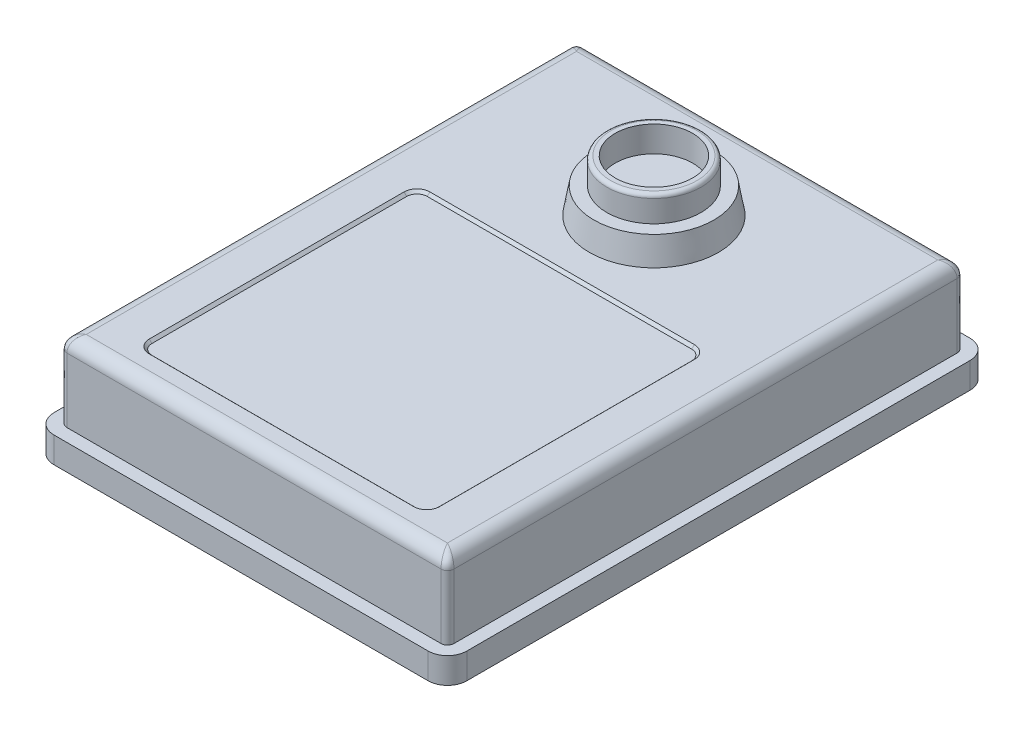
SolidWorks part; units mm, degrees
ref_plane "Front Plane" through (0, 0, 0) normal (0, 0, 1) x (1, 0, 0)
ref_plane "Top Plane" through (0, 0, 0) normal (0, 1, 0) x (1, 0, 0)
ref_plane "Right Plane" through (0, 0, 0) normal (1, 0, 0) x (0, 0, -1)
sketch "Sketch1" plane through (0, 0, 0) normal (0, 1, 0) x (1, 0, 0)
  line L1 (150, 200) -> (-150, 200)
  line L2 (150, 200) -> (150, -200)
  line L3 (150, -200) -> (-150, -200)
  line L4 (-150, 200) -> (-150, -200)
  line L5 (150, 200) -> (-150, -200) construction
  line L6 (150, -200) -> (-150, 200) construction
  point P0 (0, 0)
  dimension "D1" = 400
  dimension "D2" = 300
extrude "Boss-Extrude1" add sketch "Sketch1" along normal blind 80
fillet "Fillet1" radius 10 4 edges at (0, 80, -200) (150, 80, 0) (0, 80, 200) (-150, 80, 0)
sketch "Sketch2" plane through (0, 80, 0) normal (0, 1, 0) x (1, 0, 0)
  line L0 (140, 190) -> (-140, 190) construction
  circle A0 centre (0, 110) radius 50
  dimension "D1" = 100
  dimension "D2" = 80
extrude "Boss-Extrude2" add sketch "Sketch2" along normal blind 20 draft 10
sketch "Sketch3" plane through (0, 100, 0) normal (0, 1, 0) x (1, 0, 0)
  circle A2 centre (0, 110) radius 36.4735
  circle A3 centre (0, 110) radius 36.4735
  dimension "D1" = 10
extrude "Boss-Extrude3" add sketch "Sketch3" along normal blind 20
sketch "Sketch4" plane through (0, 120, 0) normal (0, 1, 0) x (1, 0, 0)
  circle A1 centre (0, 110) radius 30.015
  dimension "D1" = 60.03
extrude "Cut-Extrude1" cut sketch "Sketch4" against normal blind 20
fillet "Fillet3" radius 3 1 edges at (0, 120, -73.5265)
fillet "Fillet4" radius 5 8 edges at (-147.0711, 77.0711, -197.0711) (-147.0711, 77.0711, 197.0711) (147.0711, 77.0711, -197.0711) (147.0711, 77.0711, 197.0711) (-150, 35, -200) (-150, 35, 200) (150, 35, -200) (150, 35, 200)
sketch "Sketch5" plane through (0, 0, 0) normal (0, -1, 0) x (1, 0, 0)
  line L8 (-160, 195) -> (-160, -195)
  line L9 (-145, -210) -> (145, -210)
  line L10 (160, -195) -> (160, 195)
  line L11 (145, 210) -> (-145, 210)
  line L12 (-160, 195) -> (-160, -195)
  line L13 (-145, -210) -> (145, -210)
  line L14 (160, -195) -> (160, 195)
  line L15 (145, 210) -> (-145, 210)
  line L20 (-150, 195) -> (-150, -195)
  line L21 (-145, -200) -> (145, -200)
  line L22 (150, -195) -> (150, 195)
  line L23 (145, 200) -> (-145, 200)
  line L24 (-150, 195) -> (-150, -195)
  line L25 (-145, -200) -> (145, -200)
  line L26 (150, -195) -> (150, 195)
  line L27 (145, 200) -> (-145, 200)
  arc A8 (-160, -195) -> (-145, -210) centre (-145, -195) ccw
  arc A9 (145, -210) -> (160, -195) centre (145, -195) ccw
  arc A10 (160, 195) -> (145, 210) centre (145, 195) ccw
  arc A11 (-145, 210) -> (-160, 195) centre (-145, 195) ccw
  arc A12 (-160, -195) -> (-145, -210) centre (-145, -195) ccw
  arc A13 (145, -210) -> (160, -195) centre (145, -195) ccw
  arc A14 (160, 195) -> (145, 210) centre (145, 195) ccw
  arc A15 (-145, 210) -> (-160, 195) centre (-145, 195) ccw
  arc A20 (-150, -195) -> (-145, -200) centre (-145, -195) ccw
  arc A21 (145, -200) -> (150, -195) centre (145, -195) ccw
  arc A22 (150, 195) -> (145, 200) centre (145, 195) ccw
  arc A23 (-145, 200) -> (-150, 195) centre (-145, 195) ccw
  arc A24 (-150, -195) -> (-145, -200) centre (-145, -195) ccw
  arc A25 (145, -200) -> (150, -195) centre (145, -195) ccw
  arc A26 (150, 195) -> (145, 200) centre (145, 195) ccw
  arc A27 (-145, 200) -> (-150, 195) centre (-145, 195) ccw
  dimension "D1" = 10
  dimension "D2" = 0
extrude "Boss-Extrude4" add sketch "Sketch5" against normal blind 20
sketch "Sketch6" plane through (0, 80, 0) normal (0, 1, 0) x (1, 0, 0)
  line L1 (-102.4992, -178.6595) -> (102.4992, -178.6595)
  line L2 (-112.4992, -168.6595) -> (-112.4992, 28.839)
  line L3 (-102.4992, 38.839) -> (102.4992, 38.839)
  line L4 (112.4992, -168.6595) -> (112.4992, 28.839)
  line L5 (-112.4992, -178.6595) -> (112.4992, 38.839) construction
  line L6 (-112.4992, 38.839) -> (112.4992, -178.6595) construction
  arc A0 (-102.4992, -178.6595) -> (-112.4992, -168.6595) centre (-102.4992, -168.6595) cw
  arc A1 (102.4992, -178.6595) -> (112.4992, -168.6595) centre (102.4992, -168.6595) ccw
  arc A2 (102.4992, 38.839) -> (112.4992, 28.839) centre (102.4992, 28.839) cw
  arc A3 (-112.4992, 28.839) -> (-102.4992, 38.839) centre (-102.4992, 28.839) cw
  point P0 (0, -69.9102)
  dimension "D1" = 10
extrude "Cut-Extrude2" cut sketch "Sketch6" against normal blind 2 draft 46
